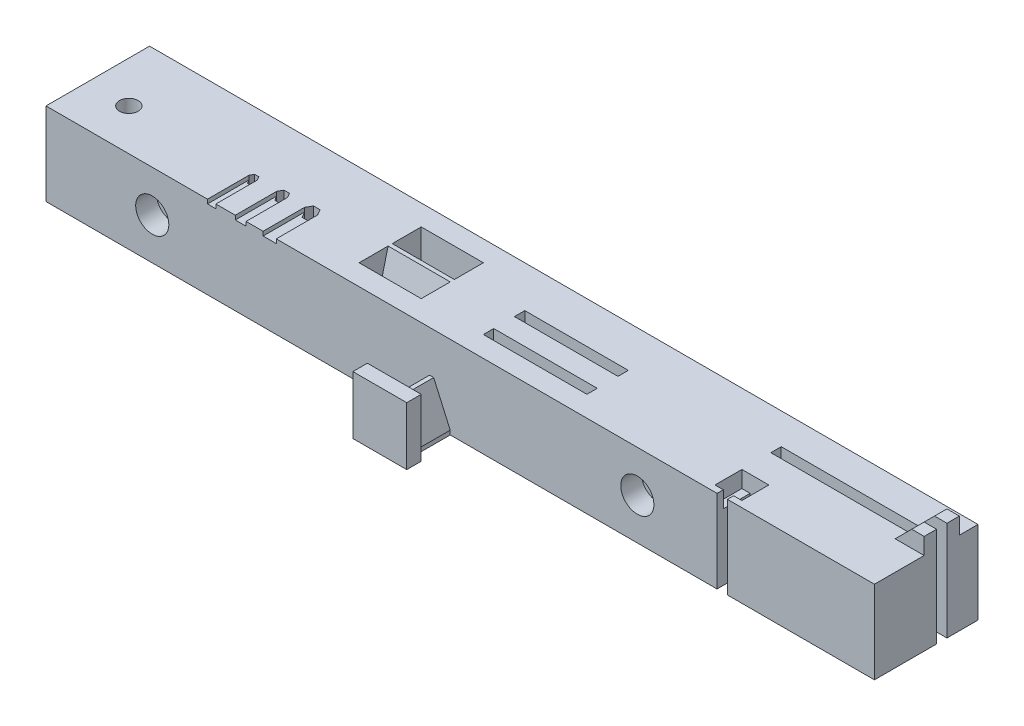
SolidWorks part; units mm, degrees
ref_plane "Piano frontale" through (0, 0, 0) normal (0, 0, 1) x (1, 0, 0)
ref_plane "Piano superiore" through (0, 0, 0) normal (0, 1, 0) x (1, 0, 0)
ref_plane "Piano destro" through (0, 0, 0) normal (1, 0, 0) x (0, 0, -1)
sketch "Schizzo1" plane through (0, 0, 0) normal (0, 0, 1) x (1, 0, 0)
  line L1 (-63.299, 14.3184) -> (136.701, 14.3184)
  line L2 (-63.299, 14.3184) -> (-63.299, -5.6816)
  line L3 (-63.299, -5.6816) -> (136.701, -5.6816)
  line L4 (136.701, 14.3184) -> (136.701, -5.6816)
  dimension "D1" = 20
  dimension "D2" = 200
extrude "Estrusione-Estrusione1" add sketch "Schizzo1" along normal blind 25
sketch "Schizzo2" plane through (0, 14.3184, 0) normal (0, 1, 0) x (1, 0, 0)
  line L0 (136.701, 0) -> (-63.299, 0) construction
  line L2 (-63.299, -25) -> (-63.299, 0) construction
  line L3 (-23.8041, -15.875) -> (-22.7938, -15.875)
  line L4 (-22.7938, -15.875) -> (-22.2886, -15)
  line L5 (-22.2886, -15) -> (-22.7938, -14.125)
  line L6 (-22.7938, -14.125) -> (-23.8041, -14.125)
  line L7 (-23.8041, -14.125) -> (-24.3093, -15)
  line L8 (-24.3093, -15) -> (-23.8041, -15.875)
  line L9 (-14.9999, -15) -> (-15.6494, -13.875)
  line L10 (-15.6494, -13.875) -> (-16.9485, -13.875)
  line L11 (-16.9485, -13.875) -> (-17.598, -15)
  line L12 (-17.598, -15) -> (-16.9485, -16.125)
  line L13 (-16.9485, -16.125) -> (-15.6494, -16.125)
  line L14 (-15.6494, -16.125) -> (-14.9999, -15)
  line L15 (-8.5051, -16.375) -> (-7.7113, -15)
  line L16 (-7.7113, -15) -> (-8.5051, -13.625)
  line L17 (-8.5051, -13.625) -> (-10.0928, -13.625)
  line L18 (-10.0928, -13.625) -> (-10.8867, -15)
  line L19 (-10.8867, -15) -> (-10.0928, -16.375)
  line L20 (-10.0928, -16.375) -> (-8.5051, -16.375)
  circle A0 centre (-53.299, -15) radius 2.25
  circle A1 centre (-23.299, -15) radius 0.875 construction
  circle A2 centre (-16.299, -15) radius 1.125 construction
  circle A3 centre (-9.299, -15) radius 1.375 construction
  dimension "D2" = 4.5
  dimension "D4" = 1.75
  dimension "D5" = 2.25
  dimension "D6" = 2.75
  dimension "D1" = 15
  dimension "D3" = 10
  dimension "D7" = 30
  dimension "D8" = 7
  dimension "D9" = 7
  dimension "D10" = 15
  dimension "D11" = 15
  dimension "D12" = 15
extrude "Taglio-Estrusione1" cut sketch "Schizzo2" against normal through all
sketch "Schizzo4" plane through (0, 14.3184, 0) normal (0, 1, 0) x (1, 0, 0)
  line L0 (136.701, -25) -> (-63.299, -25) construction
  line L1 (-24.3093, -15) -> (-22.2886, -15)
  line L2 (-24.3093, -15) -> (-24.3093, -25)
  line L3 (-24.3093, -25) -> (-22.2886, -25)
  line L4 (-22.2886, -15) -> (-22.2886, -25)
  line L5 (-17.598, -15) -> (-14.9999, -15)
  line L6 (-17.598, -15) -> (-17.598, -25)
  line L7 (-17.598, -25) -> (-14.9999, -25)
  line L8 (-14.9999, -15) -> (-14.9999, -25)
  line L10 (-10.8867, -15) -> (-7.7113, -15)
  line L11 (-10.8867, -15) -> (-10.8867, -25)
  line L12 (-10.8867, -25) -> (-7.7113, -25)
  line L13 (-7.7113, -15) -> (-7.7113, -25)
extrude "Taglio-Estrusione2" cut sketch "Schizzo4" against normal blind 1
sketch "Schizzo7" plane through (0, 14.3184, 0) normal (0, 1, 0) x (1, 0, 0)
  line L0 (136.701, -25) -> (-7.7113, -25) construction
  line L1 (7.2887, -14.5) -> (22.2887, -14.5)
  line L2 (7.2887, -14.5) -> (7.2887, -20)
  line L3 (7.2887, -20) -> (22.2887, -20)
  line L4 (22.2887, -14.5) -> (22.2887, -20)
  line L5 (7.2887, -5) -> (22.2887, -5)
  line L6 (7.2887, -5) -> (7.2887, -10.5)
  line L7 (7.2887, -10.5) -> (22.2887, -10.5)
  line L8 (22.2887, -5) -> (22.2887, -10.5)
  dimension "D1" = 15
  dimension "D2" = 15
  dimension "D3" = 15
  dimension "D4" = 4
  dimension "D5" = 5.5
  dimension "D6" = 5
  dimension "D7" = 15
extrude "Taglio-Estrusione3" cut sketch "Schizzo7" against normal through all
chamfer "Smusso1" distance 1.5 distance2 6 2 edges at (14.7887, 14.3184, 14.5) (14.7887, 14.3184, 10.5) first distance on face at (14.7887, 14.3184, 7.75)
sketch "Schizzo8" plane through (0, 14.3184, 0) normal (0, 1, 0) x (1, 0, 0)
  line L0 (7.2887, -20) -> (22.2887, -20) construction
  line L1 (37.2887, -17.5) -> (62.2887, -17.5)
  line L2 (37.2887, -17.5) -> (37.2887, -20)
  line L3 (37.2887, -20) -> (62.2887, -20)
  line L4 (62.2887, -17.5) -> (62.2887, -20)
  line L5 (37.2887, -10) -> (62.2887, -10)
  line L6 (37.2887, -10) -> (37.2887, -12.5)
  line L7 (37.2887, -12.5) -> (62.2887, -12.5)
  line L8 (62.2887, -10) -> (62.2887, -12.5)
  line L9 (22.2887, -12) -> (22.2887, -5) construction
  point P10 (22.2887, -8.5)
  dimension "D1" = 25
  dimension "D2" = 25
  dimension "D3" = 2.5
  dimension "D4" = 2.5
  dimension "D5" = 5
  dimension "D6" = 15
extrude "Taglio-Estrusione4" cut sketch "Schizzo8" against normal blind 13
sketch "Schizzo9" plane through (0, 14.3184, 0) normal (0, 1, 0) x (1, 0, 0)
  line L0 (136.701, -25) -> (136.701, 0) construction
  line L1 (96.701, -7.5) -> (136.701, -7.5)
  line L2 (96.701, -7.5) -> (96.701, -10)
  line L3 (96.701, -10) -> (136.701, -10)
  line L4 (136.701, -7.5) -> (136.701, -10)
  line L5 (136.701, 0) -> (-63.299, 0) construction
  dimension "D1" = 40
  dimension "D2" = 2.5
  dimension "D3" = 7.5
extrude "Taglio-Estrusione5" cut sketch "Schizzo9" against normal through all
sketch "Schizzo10" plane through (0, 14.3184, 0) normal (0, 1, 0) x (1, 0, 0)
  line L1 (136.701, -7.5) -> (129.701, -7.5)
  line L2 (136.701, -7.5) -> (136.701, -4.5)
  line L3 (136.701, -4.5) -> (129.701, -4.5)
  line L4 (129.701, -7.5) -> (129.701, -4.5)
  line L5 (136.701, -10) -> (129.701, -10)
  line L6 (136.701, -10) -> (136.701, -13)
  line L7 (136.701, -13) -> (129.701, -13)
  line L8 (129.701, -10) -> (129.701, -13)
  dimension "D1" = 7
  dimension "D2" = 7
  dimension "D3" = 3
  dimension "D4" = 3
extrude "Estrusione-Estrusione5" add sketch "Schizzo10" along normal blind 4
chamfer "Smusso2" distance 4 angle 45 2 edges at (129.701, 18.3184, 11.5) (129.701, 18.3184, 6)
sketch "Schizzo11" plane through (0, 14.3184, 0) normal (0, 1, 0) x (1, 0, 0)
  line L0 (136.701, -25) -> (-7.7113, -25) construction
  line L1 (98.701, -25) -> (101.201, -25)
  line L2 (98.701, -25) -> (98.701, -17)
  line L3 (98.701, -17) -> (101.201, -17)
  line L4 (101.201, -25) -> (101.201, -17)
  line L5 (96.701, -7.5) -> (96.701, -10) construction
  dimension "D1" = 2.5
  dimension "D2" = 8
  dimension "D3" = 2
extrude "Taglio-Estrusione6" cut sketch "Schizzo11" against normal through all
sketch "Schizzo12" plane through (0, 14.3184, 0) normal (0, 1, 0) x (1, 0, 0)
  line L0 (101.201, -17) -> (98.701, -17) construction
  line L1 (96.701, -17) -> (103.201, -17)
  line L2 (96.701, -17) -> (96.701, -23.5)
  line L3 (96.701, -23.5) -> (103.201, -23.5)
  line L4 (103.201, -17) -> (103.201, -23.5)
  line L7 (96.701, -7.5) -> (96.701, -10) construction
  dimension "D1" = 6.5
  dimension "D2" = 6.5
extrude "Taglio-Estrusione7" cut sketch "Schizzo12" against normal blind 4
sketch "Schizzo13" plane through (0, 0, 25) normal (0, 0, 1) x (1, 0, 0)
  line L0 (-63.299, -5.6816) -> (98.701, -5.6816) construction
  line L1 (25.2887, 4.3184) -> (34.2887, 4.3184)
  line L2 (25.2887, 4.3184) -> (25.2887, -5.6816)
  line L3 (25.2887, -5.6816) -> (34.2887, -5.6816)
  line L4 (34.2887, 4.3184) -> (34.2887, -5.6816)
  dimension "D1" = 10
  dimension "D2" = 3
  dimension "D3" = 9
extrude "Estrusione-Estrusione9" add sketch "Schizzo13" along normal blind 9 contours L2 L3 L4 L1
sketch "Schizzo14" plane through (0, 0, 34) normal (0, 0, 1) x (1, 0, 0)
  line L0 (25.2887, -5.6816) -> (34.2887, -5.6816) construction
  line L1 (23.2887, 8.3184) -> (36.2887, 8.3184)
  line L2 (23.2887, 8.3184) -> (23.2887, -5.6816)
  line L3 (23.2887, -5.6816) -> (36.2887, -5.6816)
  line L4 (36.2887, 8.3184) -> (36.2887, -5.6816)
  line L5 (25.2887, 4.3184) -> (25.2887, -5.6816) construction
  dimension "D1" = 13
  dimension "D2" = 14
  dimension "D3" = 2
extrude "Estrusione-Estrusione10" add sketch "Schizzo14" along normal blind 3.5
chamfer "Smusso3" distance 9 distance2 4 1 edges at (34.2887, 4.3184, 29.5) first distance on face at (34.2887, 0.5684, 30.625)
chamfer "Smusso4" distance 4 distance2 9 1 edges at (25.2887, 4.3184, 29.5) first distance on face at (27.7887, 4.3184, 29.5)
sketch "Schizzo16" plane through (0, 0, 25) normal (0, 0, 1) x (1, 0, 0)
  line L2 (-24.3093, 14.3184) -> (-63.299, 14.3184) construction
  line L3 (98.701, 14.3184) -> (-7.7113, 14.3184) construction
  circle A0 centre (-37.649, 4.3184) radius 2.25
  circle A1 centre (79.451, 4.3184) radius 2.25
  dimension "D3" = 4.5
  dimension "D4" = 4.5
  dimension "D1" = 17.25
  dimension "D2" = 13.4
  dimension "D5" = 10
  dimension "D6" = 10
extrude "Taglio-Estrusione8" cut sketch "Schizzo16" against normal through all
sketch "Schizzo17" plane through (0, 0, 25) normal (0, 0, 1) x (1, 0, 0)
  circle A0 centre (-37.649, 4.3184) radius 4
  circle A1 centre (79.451, 4.3184) radius 4
  dimension "D1" = 8
  dimension "D2" = 8
extrude "Taglio-Estrusione9" cut sketch "Schizzo17" against normal blind 5
